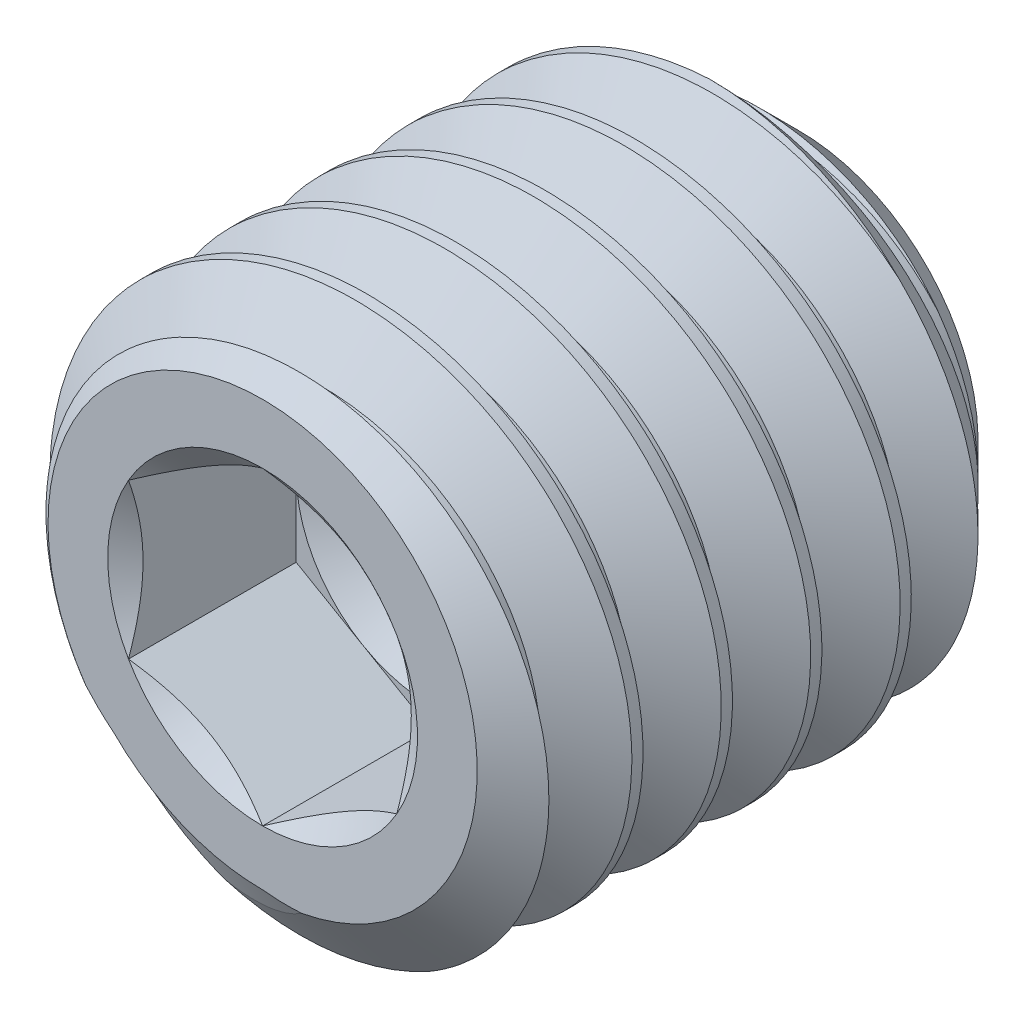
SolidWorks part; units mm, degrees
ref_plane "Front" through (0, 0, 0) normal (0, 0, 1) x (1, 0, 0)
ref_plane "Top" through (0, 0, 0) normal (0, 1, 0) x (1, 0, 0)
ref_plane "Right" through (0, 0, 0) normal (1, 0, 0) x (0, 0, -1)
sketch "Sketch22" plane through (0, 0, 0) normal (1, 0, 0) x (0, 0, -1)
  line L0 (-3, 0) -> (-3, 2.4)
  line L1 (-3, 2.4) -> (-2.5799, 3)
  line L2 (-2.5799, 3) -> (2, 3)
  line L3 (2, 3) -> (3, 2)
  line L4 (-0.2899, 3) -> (-0.2899, -3) construction
  line L5 (3, 0) -> (-3, 0)
  line L6 (-3, 2.4) -> (-3, -2.4) construction
  line L7 (3, 0) -> (3, 2)
  point P11 (-0.2899, 0)
  dimension "D1" = 4.8
  dimension "Dia" = 6
  dimension "D2" = 1
  dimension "Length" = 6
  dimension "D3" = 35
  dimension "D6" = 45
revolve "Revolve1" add sketch "Sketch22" angle 360 about L5
ref_plane "Plane1" through (0, 0, -3) normal (0, 0, 1) x (1, 0, 0)
sketch "Sketch27" plane through (0, 0, -3) normal (0, 0, 1) x (1, 0, 0)
  circle A0 centre (0, 0) radius 3 construction
  circle A1 centre (0, 0) radius 3
curve "Helix/Spiral1" pitch 1 height 7 radius 3 centre (0, 0, -3) axis (0, 0, 1) start towards (0, 1, 0)
sketch "Sketch28" plane through (0, 0, 0) normal (1, 0, 0) x (0, 0, -1)
  line L0 (3, 3) -> (3.875, 3)
  line L1 (3.875, 3) -> (3.5, 2.3505)
  line L2 (3.5, 2.3505) -> (3.375, 2.3505)
  line L3 (3.375, 2.3505) -> (3, 3)
  line L4 (3.1875, 2.6752) -> (3.6875, 2.6752) construction
  line L6 (-2.5799, 3) -> (2, 3) construction
  dimension "D1" = 0.125
  dimension "D2" = 0.5
  dimension "D3" = 60
sweep "Cut-Sweep2" cut profiles "Sketch28" path "Helix/Spiral1" align with end faces yes
sketch "Sketch23" plane through (0, 0, 3) normal (0, 0, 1) x (1, 0, 0)
  line L1 (0, 1.7321) -> (-1.5, 0.866)
  line L2 (-1.5, 0.866) -> (-1.5, -0.866)
  line L3 (-1.5, -0.866) -> (0, -1.7321)
  line L4 (0, -1.7321) -> (1.5, -0.866)
  line L5 (1.5, -0.866) -> (1.5, 0.866)
  line L6 (1.5, 0.866) -> (0, 1.7321)
  circle A0 centre (0, 0) radius 1.5 construction
  dimension "Hex" = 3
extrude "Cut-Extrude10" cut sketch "Sketch23" against normal blind 1.875
sketch "Sketch24" plane through (0, 0, 3) normal (0, 0, 1) x (1, 0, 0)
  circle A0 centre (0, 0) radius 1.7321
extrude "Cut-Extrude11" cut sketch "Sketch24" against normal through all draft 55
sketch "Sketch26" plane through (0, 0, 1.125) normal (0, 0, 1) x (1, 0, 0)
  circle A0 centre (0, 0) radius 1.5 construction
  circle A1 centre (0, 0) radius 1.5
extrude "Cut-Extrude12" cut sketch "Sketch26" against normal through all draft 60
sketch "Sketch30" plane through (0, 0, 0) normal (1, 0, 0) x (0, 0, -1)
  line L0 (-2.5799, 3) -> (2, 3) construction
  line L1 (-3, 0) -> (-3, 2.4) construction
  line L2 (3, 0) -> (3, 2) construction
  point P0 (-3, 3)
  point P1 (3, 3)
  point P2 (3, -3)
  point P11 (0.5, -3)
  dimension "D1" = 2.5
equation "\"D1@Sketch28\" = \"D4@Helix/Spiral1\" * .125"
equation "\"D2@Sketch28\" = \"D4@Helix/Spiral1\" * .5"
equation "\"D3@Helix/Spiral1\" = \"Length@Sketch22\" + \"D4@Helix/Spiral1\""
equation "\"D1@Sketch30\" = \"D4@Helix/Spiral1\" * 2.5"
equation "\"hex Depth@Cut-Extrude10\" = \"Hex@Sketch23\" * .625"
equation "\"D1@Sketch22\" = \"Dia@Sketch22\" * .8"
equation "\"D2@Sketch22\" = \"D4@Helix/Spiral1\""
